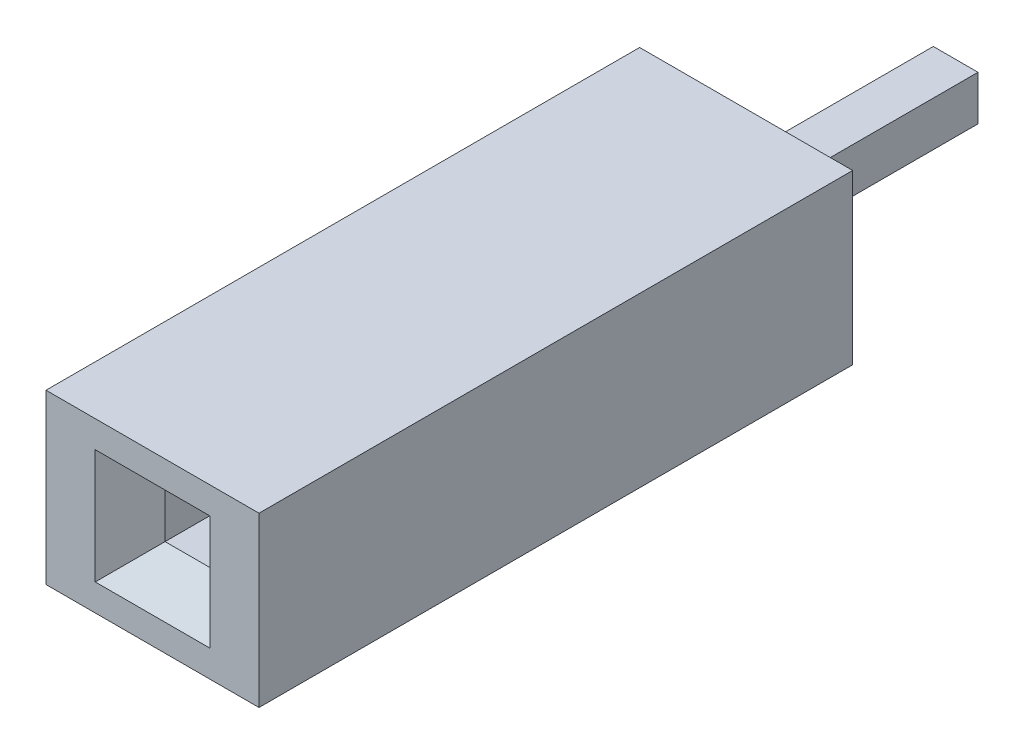
SolidWorks part; units mm, degrees
ref_plane "Front Plane" through (0, 0, 0) normal (0, 0, 1) x (1, 0, 0)
ref_plane "Top Plane" through (0, 0, 0) normal (0, 1, 0) x (1, 0, 0)
ref_plane "Right Plane" through (0, 0, 0) normal (1, 0, 0) x (0, 0, -1)
sketch "Sketch1" plane through (0, 0, 0) normal (0, 0, 1) x (1, 0, 0)
  line L1 (-1.525, 1.205) -> (1.525, 1.205)
  line L2 (-1.525, 1.205) -> (-1.525, -1.205)
  line L3 (-1.525, -1.205) -> (1.525, -1.205)
  line L4 (1.525, 1.205) -> (1.525, -1.205)
  line L9 (-0.32, 0.32) -> (0.32, 0.32)
  line L10 (-0.32, 0.32) -> (-0.32, -0.32)
  line L11 (-0.32, -0.32) -> (0.32, -0.32)
  line L12 (0.32, 0.32) -> (0.32, -0.32)
  dimension "D1" = 3.05
  dimension "D2" = 2.41
  dimension "D3" = 1.205
  dimension "D4" = 1.525
  dimension "D5" = 0.64
  dimension "D6" = 0.64
  dimension "D7" = 0.32
  dimension "D8" = 0.32
sketch "Sketch2" plane through (0, 0, 0) normal (1, 0, 0) x (0, 0, -1)
  line L0 (0, 0.32) -> (0, -0.32) construction
  line L1 (0, -0.32) -> (1.2, -0.32)
  line L2 (0, -0.32) -> (0, 0.32)
  line L5 (0, 0.32) -> (1.84, 0.32)
  line L7 (1.2, -0.32) -> (1.2, -3.745)
  line L8 (1.2, -3.745) -> (1.84, -3.745)
  line L9 (1.84, 0.32) -> (1.84, -3.745)
  line L11 (0, 0.32) -> (3.2, 0.32)
  line L12 (0, 0.32) -> (0, -0.32)
  line L13 (0, -0.32) -> (3.2, -0.32)
  line L14 (3.2, 0.32) -> (3.2, -0.32)
  dimension "D1" = 1.84
  dimension "D2" = 3.745
  dimension "D3" = 0.64
  dimension "D4" = 0.32
  dimension "D5" = 3.2
  dimension "D6" = 0.64
extrude "Boss-Extrude1" add sketch "Sketch1" along normal blind 8.5 contours L3 L4 L1 L2
extrude "Cut-Extrude1" cut sketch "Sketch1<3>" against normal blind 5 from surface contours L10 L11 L12 L9 starting at face at (0, 0, 8.5)
sketch "Sketch1<3>" plane through (0, 0, 0) normal (0, 0, 1) x (1, 0, 0) same geometry as "Sketch1"
chamfer "Chamfer1" distance 0.5 angle 45 4 edges at (0.32, 0, 8.5) (0, 0.32, 8.5) (-0.32, 0, 8.5) (0, -0.32, 8.5)
extrude "Boss-Extrude2" add sketch "Sketch2" along normal mid plane 0.64 contours L14 L11 L9 L13 | L1 L13 L9 L5 L2 region at (0, 0, -0.92) region at (0, 0, -2.52)
chamfer "Chamfer2" distance 0.2 angle 45 4 edges at (0.32, 0, -3.2) (0, -0.32, -3.2) (-0.32, 0, -3.2) (0, 0.32, -3.2)
